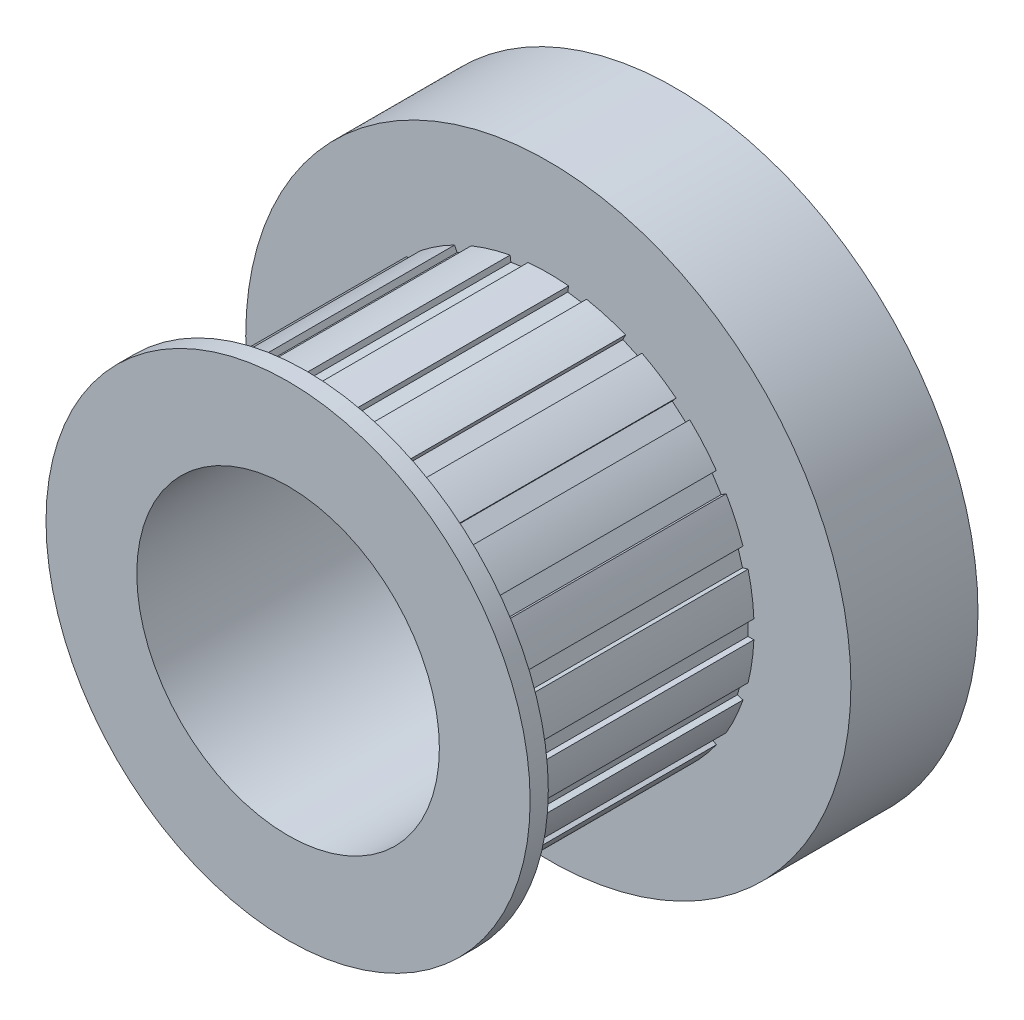
SolidWorks part; units mm, degrees
ref_plane "Front Plane" through (0, 0, 0) normal (0, 0, 1) x (1, 0, 0)
ref_plane "Top Plane" through (0, 0, 0) normal (0, 1, 0) x (1, 0, 0)
ref_plane "Right Plane" through (0, 0, 0) normal (1, 0, 0) x (0, 0, -1)
sketch "Sketch1" plane through (0, 0, 0) normal (0, 0, 1) x (1, 0, 0)
  circle A0 centre (0, 0) radius 10.16
  dimension "D1" = 20.32
extrude "Boss-Extrude1" add sketch "Sketch1" against normal blind 0.762
sketch "Sketch2" plane through (0, 0, -0.762) normal (0, 0, -1) x (-1, 0, 0)
  circle A0 centre (0, 0) radius 8.636
  dimension "D1" = 17.272
extrude "Boss-Extrude2" add sketch "Sketch2" along normal blind 10.16
sketch "Sketch3" plane through (0, 0, -10.922) normal (0, 0, -1) x (-1, 0, 0)
  circle A0 centre (0, 0) radius 12.7
  dimension "D1" = 25.4
extrude "Boss-Extrude3" add sketch "Sketch3" along normal blind 5.334
sketch "Sketch4" plane through (0, 0, 0) normal (0, 0, 1) x (1, 0, 0)
  circle A0 centre (0, 0) radius 6.35
  dimension "D1" = 12.7
extrude "Cut-Extrude1" cut sketch "Sketch4" against normal blind 25.654
ref_plane "Plane2" through (-8.636, 0, 0) normal (-1, 0, 0) x (0, 0, 1)
sketch "Sketch5" plane through (-8.636, 0, 0) normal (-1, 0, 0) x (0, 0, 1)
  line L0 (-10.922, -8.636) -> (-10.922, 8.636) construction
  line L1 (-10.922, 0.381) -> (-0.762, 0.381)
  line L2 (-10.922, 0.381) -> (-10.922, -0.381)
  line L3 (-10.922, -0.381) -> (-0.762, -0.381)
  line L4 (-0.762, 0.381) -> (-0.762, -0.381)
  line L5 (-0.762, 8.636) -> (-0.762, -8.636) construction
  point P8 (-10.922, 0)
  dimension "D1" = 0.762
extrude "Cut-Extrude2" cut sketch "Sketch5" against normal blind 0.254
ref_axis "Axis1" through (0, 0, -16.256) along (0, 0, 1)
pattern_circular "CirPattern1" count 22 over 360 about axis through (0, 0, -16.256) along (0, 0, 1) of "Cut-Extrude2"
